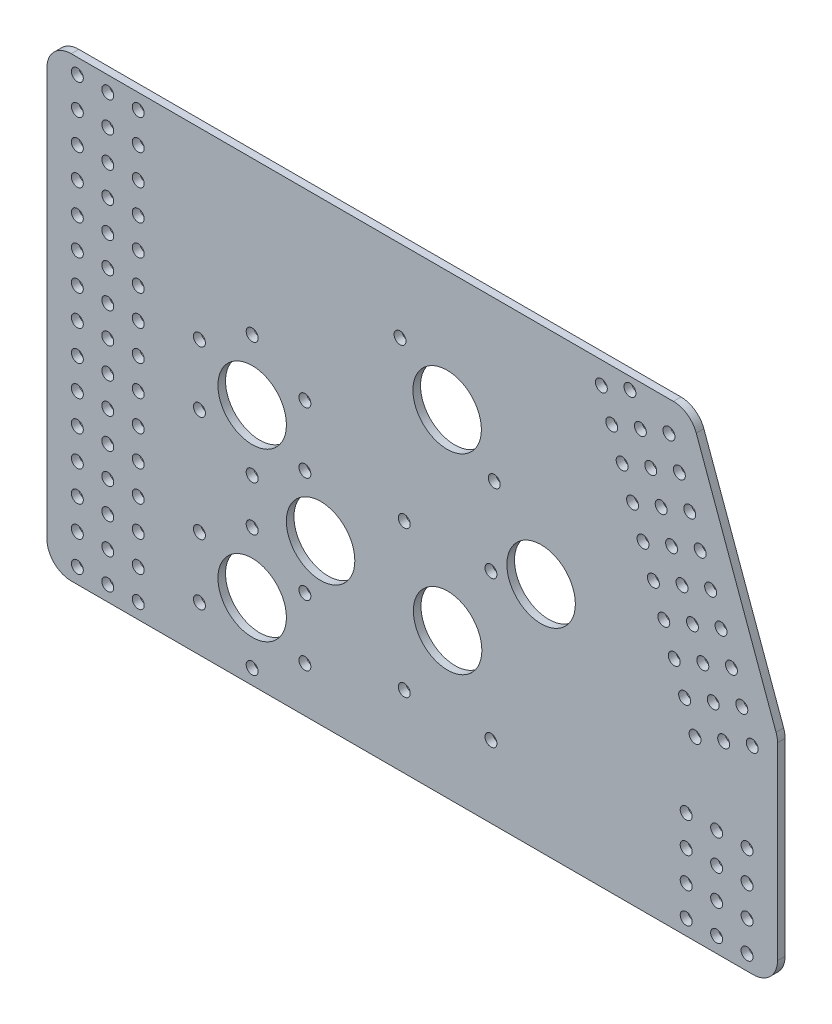
SolidWorks part; units mm, degrees
ref_plane "Front Plane" through (0, 0, 0) normal (0, 0, 1) x (1, 0, 0)
ref_plane "Top Plane" through (0, 0, 0) normal (0, 1, 0) x (1, 0, 0)
ref_plane "Right Plane" through (0, 0, 0) normal (1, 0, 0) x (0, 0, -1)
sketch "Sketch6" plane through (0, 0, 0) normal (0, 0, 1) x (1, 0, 0)
  line L0 (-62.0347, 275.0603) -> (206.4353, 275.0603)
  line L3 (206.4353, 275.0603) -> (242.7653, 175.2445)
  line L4 (242.7653, 175.2445) -> (242.7653, 84.5603)
  line L6 (242.7653, 84.5603) -> (-62.0347, 84.5603)
  line L7 (-62.0347, 84.5603) -> (-62.0347, 275.0603)
  line L8 (-49.3347, 268.7103) -> (-36.6347, 268.7103) construction
  line L9 (-49.3347, 268.7103) -> (-49.3347, 256.0103) construction
  line L10 (105.1393, -854.8604) -> (105.1393, 49145.1396) construction
  line L11 (169.2687, 265.7779) -> (173.6123, 253.8438) construction
  line L12 (204.6653, 129.0103) -> (204.6653, 116.3103) construction
  line L13 (23.6016, 116.2566) -> (23.6016, 141.6566) construction
  line L14 (23.6016, 185.8526) -> (23.6016, 211.2526) construction
  line L15 (-894.8607, 145.1396) -> (49105.1393, 145.1396) construction
  circle A0 centre (123.2241, 114.6088) radius 2.4892
  circle A1 centre (87.0545, 114.6088) radius 2.4892
  circle A2 centre (-49.3347, 268.7103) radius 2.4892
  circle A3 centre (-49.3347, 90.9103) radius 2.4892
  circle A4 centre (-36.6347, 268.7103) radius 2.4892
  circle A5 centre (-23.9347, 268.7103) radius 2.4892
  circle A6 centre (-36.6347, 256.0103) radius 2.4892
  circle A7 centre (-23.9347, 256.0103) radius 2.4892
  circle A8 centre (-36.6347, 243.3103) radius 2.4892
  circle A9 centre (-23.9347, 243.3103) radius 2.4892
  circle A10 centre (-36.6347, 230.6103) radius 2.4892
  circle A11 centre (-23.9347, 230.6103) radius 2.4892
  circle A12 centre (-36.6347, 217.9103) radius 2.4892
  circle A13 centre (-23.9347, 217.9103) radius 2.4892
  circle A14 centre (-36.6347, 205.2103) radius 2.4892
  circle A15 centre (-23.9347, 205.2103) radius 2.4892
  circle A16 centre (-36.6347, 192.5103) radius 2.4892
  circle A17 centre (-23.9347, 192.5103) radius 2.4892
  circle A18 centre (-36.6347, 179.8103) radius 2.4892
  circle A19 centre (-23.9347, 179.8103) radius 2.4892
  circle A20 centre (-36.6347, 167.1103) radius 2.4892
  circle A21 centre (-23.9347, 167.1103) radius 2.4892
  circle A22 centre (-36.6347, 154.4103) radius 2.4892
  circle A23 centre (-23.9347, 154.4103) radius 2.4892
  circle A24 centre (-36.6347, 141.7103) radius 2.4892
  circle A25 centre (-23.9347, 141.7103) radius 2.4892
  circle A26 centre (-36.6347, 129.0103) radius 2.4892
  circle A27 centre (-23.9347, 129.0103) radius 2.4892
  circle A28 centre (-36.6347, 116.3103) radius 2.4892
  circle A29 centre (-23.9347, 116.3103) radius 2.4892
  circle A30 centre (-36.6347, 103.6103) radius 2.4892
  circle A31 centre (-23.9347, 103.6103) radius 2.4892
  circle A32 centre (-36.6347, 90.9103) radius 2.4892
  circle A33 centre (-23.9347, 90.9103) radius 2.4892
  circle A34 centre (-49.3347, 256.0103) radius 2.4892
  circle A35 centre (-49.3347, 243.3103) radius 2.4892
  circle A36 centre (-49.3347, 230.6103) radius 2.4892
  circle A37 centre (-49.3347, 217.9103) radius 2.4892
  circle A38 centre (-49.3347, 205.2103) radius 2.4892
  circle A39 centre (-49.3347, 192.5103) radius 2.4892
  circle A40 centre (-49.3347, 179.8103) radius 2.4892
  circle A41 centre (-49.3347, 167.1103) radius 2.4892
  circle A42 centre (-49.3347, 154.4103) radius 2.4892
  circle A43 centre (-49.3347, 141.7103) radius 2.4892
  circle A44 centre (-49.3347, 129.0103) radius 2.4892
  circle A45 centre (-49.3347, 116.3103) radius 2.4892
  circle A46 centre (-49.3347, 103.6103) radius 2.4892
  circle A47 centre (-49.3347, 90.9103) radius 2.4892
  circle A48 centre (169.2687, 265.7779) radius 2.4892
  circle A49 centre (181.2028, 270.1215) radius 2.4892
  circle A50 centre (197.4805, 262.5311) radius 2.4892
  circle A51 centre (173.6123, 253.8438) radius 2.4892
  circle A52 centre (185.5464, 258.1874) radius 2.4892
  circle A53 centre (201.8242, 250.597) radius 2.4892
  circle A54 centre (177.956, 241.9097) radius 2.4892
  circle A55 centre (189.8901, 246.2533) radius 2.4892
  circle A56 centre (206.1678, 238.6629) radius 2.4892
  circle A57 centre (182.2996, 229.9756) radius 2.4892
  circle A58 centre (194.2337, 234.3192) radius 2.4892
  circle A59 centre (210.5115, 226.7288) radius 2.4892
  circle A60 centre (186.6433, 218.0415) radius 2.4892
  circle A61 centre (198.5774, 222.3851) radius 2.4892
  circle A62 centre (214.8551, 214.7947) radius 2.4892
  circle A63 centre (190.9869, 206.1074) radius 2.4892
  circle A64 centre (202.921, 210.451) radius 2.4892
  circle A65 centre (219.1988, 202.8606) radius 2.4892
  circle A66 centre (195.3306, 194.1733) radius 2.4892
  circle A67 centre (207.2647, 198.5169) radius 2.4892
  circle A68 centre (223.5424, 190.9265) radius 2.4892
  circle A69 centre (199.6743, 182.2392) radius 2.4892
  circle A70 centre (211.6083, 186.5828) radius 2.4892
  circle A71 centre (227.8861, 178.9924) radius 2.4892
  circle A72 centre (204.0179, 170.3051) radius 2.4892
  circle A73 centre (215.952, 174.6488) radius 2.4892
  circle A74 centre (232.2298, 167.0583) radius 2.4892
  circle A75 centre (208.3616, 158.371) radius 2.4892
  circle A76 centre (220.2957, 162.7147) radius 2.4892
  circle A78 centre (236.5734, 155.1242) radius 2.4892 [skipped]
  circle A79 centre (204.6653, 129.0103) radius 2.4892
  circle A80 centre (217.3653, 129.0103) radius 2.4892
  circle A81 centre (230.0653, 129.0103) radius 2.4892
  circle A82 centre (204.6653, 116.3103) radius 2.4892
  circle A83 centre (217.3653, 116.3103) radius 2.4892
  circle A84 centre (230.0653, 116.3103) radius 2.4892
  circle A85 centre (204.6653, 103.6103) radius 2.4892
  circle A86 centre (217.3653, 103.6103) radius 2.4892
  circle A87 centre (230.0653, 103.6103) radius 2.4892
  circle A88 centre (204.6653, 90.9103) radius 2.4892
  circle A89 centre (217.3653, 90.9103) radius 2.4892
  circle A90 centre (230.0653, 90.9103) radius 2.4892
  circle A91 centre (23.6016, 185.8526) radius 14.2875
  circle A92 centre (52.1422, 151.0564) radius 14.2875
  circle A93 centre (23.6016, 116.2566) radius 14.2875
  circle A94 centre (105.1393, 145.1396) radius 14.2875
  circle A95 centre (104.9447, 224.8273) radius 14.2875
  circle A96 centre (144.1424, 181.3926) radius 14.2875
  circle A99 centre (85.284, 241.0108) radius 2.4892
  circle A100 centre (23.6016, 141.6566) radius 2.4892
  circle A101 centre (45.5987, 128.9566) radius 2.4892
  circle A102 centre (45.5987, 103.5566) radius 2.4892
  circle A103 centre (23.6016, 90.8566) radius 2.4892
  circle A104 centre (1.6046, 103.5566) radius 2.4892
  circle A105 centre (1.6046, 128.9566) radius 2.4892
  circle A106 centre (23.6016, 211.2526) radius 2.4892
  circle A107 centre (45.5987, 198.5526) radius 2.4892
  circle A108 centre (45.5987, 173.1526) radius 2.4892
  circle A109 centre (23.6016, 160.4526) radius 2.4892
  circle A110 centre (1.6046, 173.1526) radius 2.4892
  circle A111 centre (1.6046, 198.5526) radius 2.4892
  circle A112 centre (123.2241, 175.6704) radius 2.4892
  circle A113 centre (87.0545, 175.6704) radius 2.4892
  circle A116 centre (124.6065, 208.849) radius 2.4892
  dimension "D1" = 4.9784
  dimension "D2" = 6.35
  dimension "D3" = 4.9784
  dimension "D10" = 4.9784
  dimension "D11" = 4.9784
  dimension "D12" = 4.9784
  dimension "D15" = 4.9784
  dimension "D16" = 4.9784
  dimension "D17" = 4.9784
  dimension "D20" = 4.9784
  dimension "D21" = 28.575
  dimension "D22" = 28.575
  dimension "D23" = 28.575
  dimension "D24" = 28.575
  dimension "D25" = 28.575
  dimension "D26" = 28.575
  dimension "D28" = 4.9784
  dimension "D32" = 4.9784
  dimension "D35" = 4.9784
  dimension "D38" = 4.9784
  dimension "D4" = 12.7
  dimension "D5" = 3
  dimension "D7" = 12.7
  dimension "D8" = 12.7
  dimension "D9" = 6.35
  dimension "D14" = 12.7
  dimension "D19" = 12.7
  dimension "D29" = 25.4
  dimension "D31" = 25.4
  dimension "D33" = 6
  dimension "D34" = 25.4
  dimension "D36" = 18.0848
  dimension "D37" = 30.5308
  dimension "D39" = 19.6607
  dimension "D40" = 16.1835
  dimension "D42" = 15.9782
  dimension "D43" = 19.6618
  dimension "D6" = 15
  dimension "D13" = 10
  dimension "D18" = 4
  dimension "D30" = 6
extrude "Boss-Extrude1" add sketch "Sketch6" along normal blind 3.175
fillet "Fillet1" radius 10.16 5 edges at (242.7653, 84.5603, 1.5875) (242.7653, 175.2445, 1.5875) (206.4353, 275.0603, 1.5875) (-62.0347, 84.5603, 1.5875) (-62.0347, 275.0603, 1.5875)
